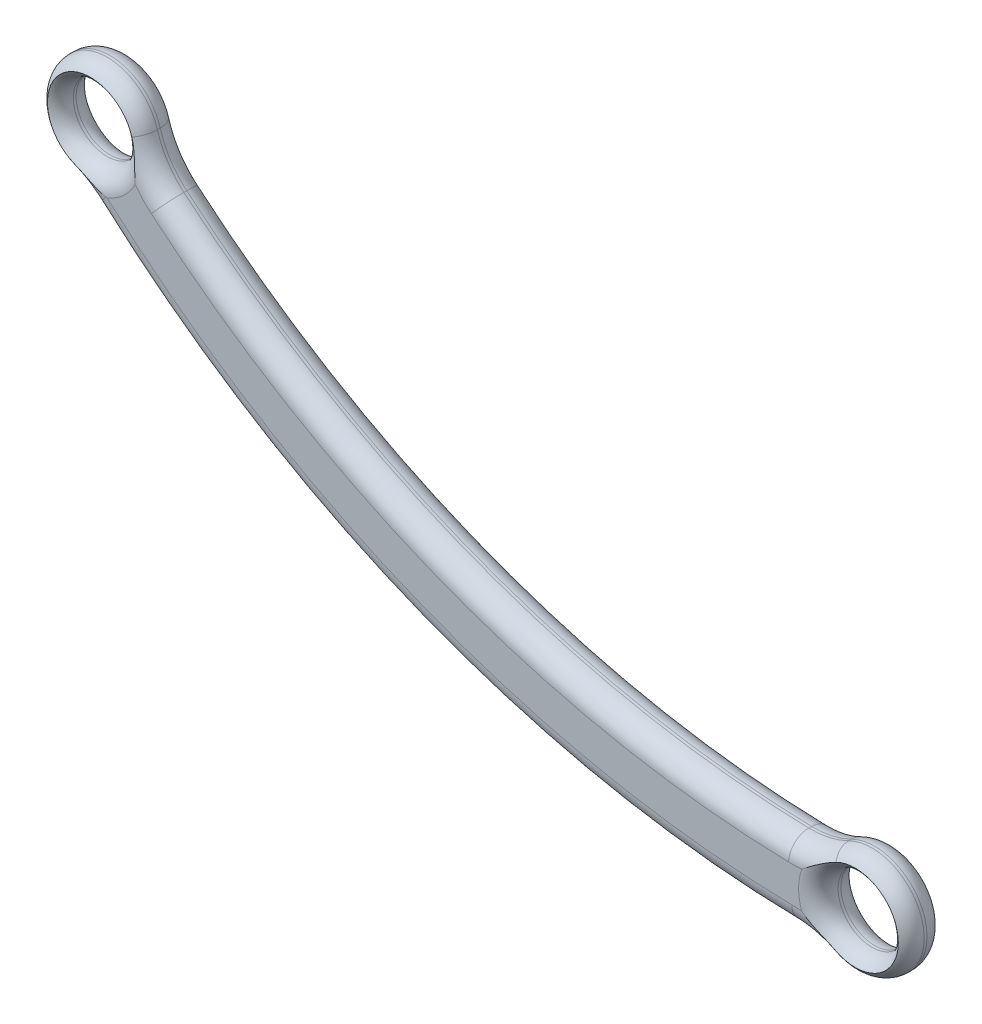
SolidWorks part; units mm, degrees
ref_plane "Front Plane" through (0, 0, 0) normal (0, 0, 1) x (1, 0, 0)
ref_plane "Top Plane" through (0, 0, 0) normal (0, 1, 0) x (1, 0, 0)
ref_plane "Right Plane" through (0, 0, 0) normal (1, 0, 0) x (0, 0, -1)
sketch "Sketch1" plane through (0, 0, 0) normal (0, 0, 1) x (1, 0, 0)
  line L0 (0, 0) -> (32.8847, 0) construction
  line L1 (0, 0) -> (-26.3159, 21.5473) construction
  line L2 (0, 0) -> (24.6472, 67.7177) construction
  line L3 (-26.3159, 21.5473) -> (32.8847, 0) construction
  arc A0 (-20.1889, 18.4244) -> (27.7437, 0) centre (27.4961, 70.9185) ccw
  arc A1 (-24.4347, 15.1114) -> (27.7334, -5.3126) centre (27.4961, 70.9185) ccw
  arc A2 (27.7334, -5.3126) -> (27.7437, 0) centre (30.3142, -2.6613) ccw
  arc A3 (-20.1889, 18.4244) -> (-24.4347, 15.1114) centre (-23.8729, 18.7685) ccw
  circle A4 centre (-23.8729, 18.7685) radius 2.4
  circle A5 centre (30.3142, -2.6613) radius 2.4
  dimension "D3" = 4.8
  dimension "D4" = 4.8
  dimension "D5" = 3.7
  dimension "D6" = 3.7
  dimension "D1" = 20
  dimension "D2" = 63
extrude "Boss-Extrude1" add sketch "Sketch1" along normal blind 3
fillet "Fillet1" radius 6 4 edges at (-20.1889, 18.4244, 1.5) (-24.4347, 15.1114, 1.5) (27.7334, -5.3126, 1.5) (27.7437, 0, 1.5)
fillet "Fillet2" radius 1.4 20 edges at (32.7142, -2.6613, 0) (-21.4729, 18.7685, 0) (-24.3076, 14.8577, 0) (-0.4838, 0.0075, 0) (27.3592, -5.4782, 0) (34.0142, -2.6792, 0) (27.29, 0.1617, 0) (2.2504, 4.6452, 0) (-19.593, 18.2023, 0) (-26.3556, 21.5119, 0) (32.7142, -2.6613, 3) (27.29, 0.1617, 3) (34.0142, -2.6792, 3) (27.3592, -5.4782, 3) (-0.4838, 0.0075, 3) (-24.3076, 14.8577, 3) (-26.3556, 21.5119, 3) (-19.593, 18.2023, 3) (2.2504, 4.6452, 3) (-21.4729, 18.7685, 3)
scale "Scale1" scale about centroid uniform scaling yes scale factor 1.15
